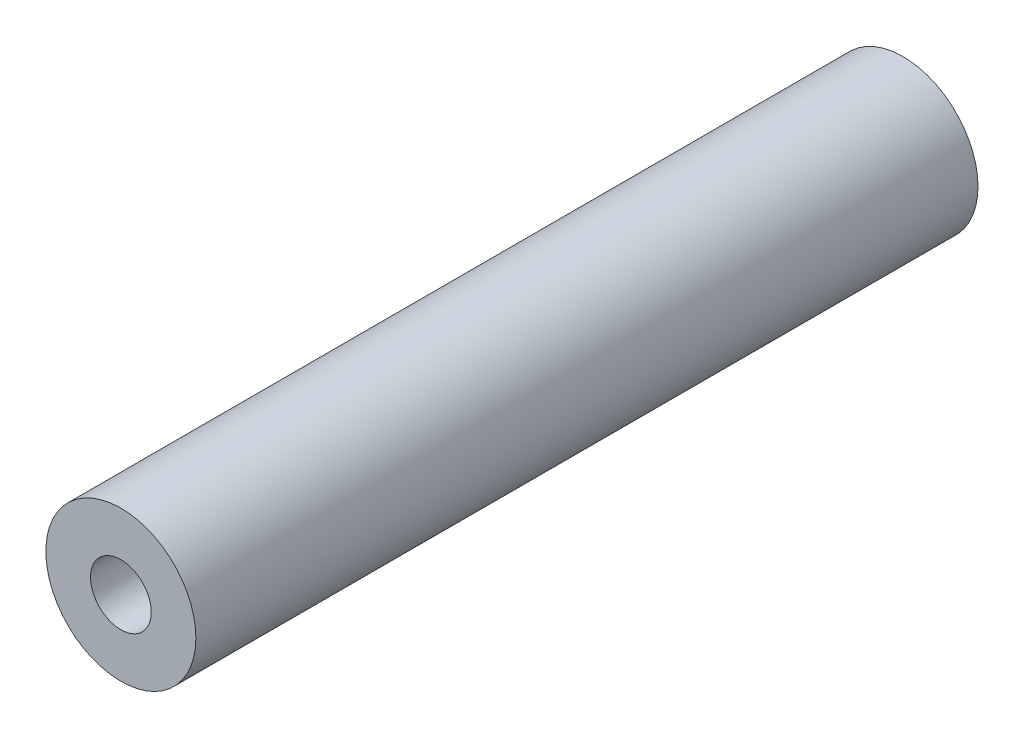
SolidWorks part; units mm, degrees
material "6061-T6 (SS)"
ref_plane "Front Plane" through (0, 0, 0) normal (0, 0, 1) x (1, 0, 0)
ref_plane "Top Plane" through (0, 0, 0) normal (0, 1, 0) x (1, 0, 0)
ref_plane "Right Plane" through (0, 0, 0) normal (1, 0, 0) x (0, 0, -1)
sketch "Sketch1" plane through (0, 0, 0) normal (0, 0, 1) x (1, 0, 0)
  circle A0 centre (0, 0) radius 6.4
  dimension "D1" = 12.8
extrude "Boss-Extrude1" add sketch "Sketch1" along normal blind 66.73
hole_wizard "#6 (0.204) Diameter Hole1" positions "Sketch2" profile "Sketch3" hole size "#6" standard "ANSI Inch"
sketch "Sketch2" plane through (0, 0, 0) normal (0, 0, -1) x (-1, 0, 0)
  point P0 (0, 0)
sketch "Sketch3" plane through (0, 0, 0) normal (1, 0, 0) x (0, 1, 0)
  line L0 (0, 0) -> (0, 31.5567)
  line L1 (0, 31.5567) -> (2.5908, 30)
  line L2 (2.5908, 30) -> (2.5908, 0)
  line L5 (2.5908, 0) -> (0, 0)
  line L10 (0, 31.5567) -> (-2.5908, 30) construction
  line L11 (0, -6.35) -> (0, 107.95) construction
  dimension "Hole Dia." = 5.1816
  dimension "Hole Depth" = 30
  dimension "Drill Angle" = 118
hole_wizard "#6 (0.204) Diameter Hole2" positions "Sketch4" profile "Sketch5" hole size "#6" standard "ANSI Inch"
sketch "Sketch4" plane through (0, 0, 66.73) normal (0, 0, 1) x (1, 0, 0)
  point P0 (0, 0)
sketch "Sketch5" plane through (0, 0, 66.73) normal (1, 0, 0) x (0, -1, 0)
  line L0 (0, 0) -> (0, 31.5567)
  line L1 (0, 31.5567) -> (2.5908, 30)
  line L2 (2.5908, 30) -> (2.5908, 0)
  line L5 (2.5908, 0) -> (0, 0)
  line L10 (0, 31.5567) -> (-2.5908, 30) construction
  line L11 (0, -6.35) -> (0, 107.95) construction
  dimension "Hole Dia." = 5.1816
  dimension "Hole Depth" = 30
  dimension "Drill Angle" = 118
